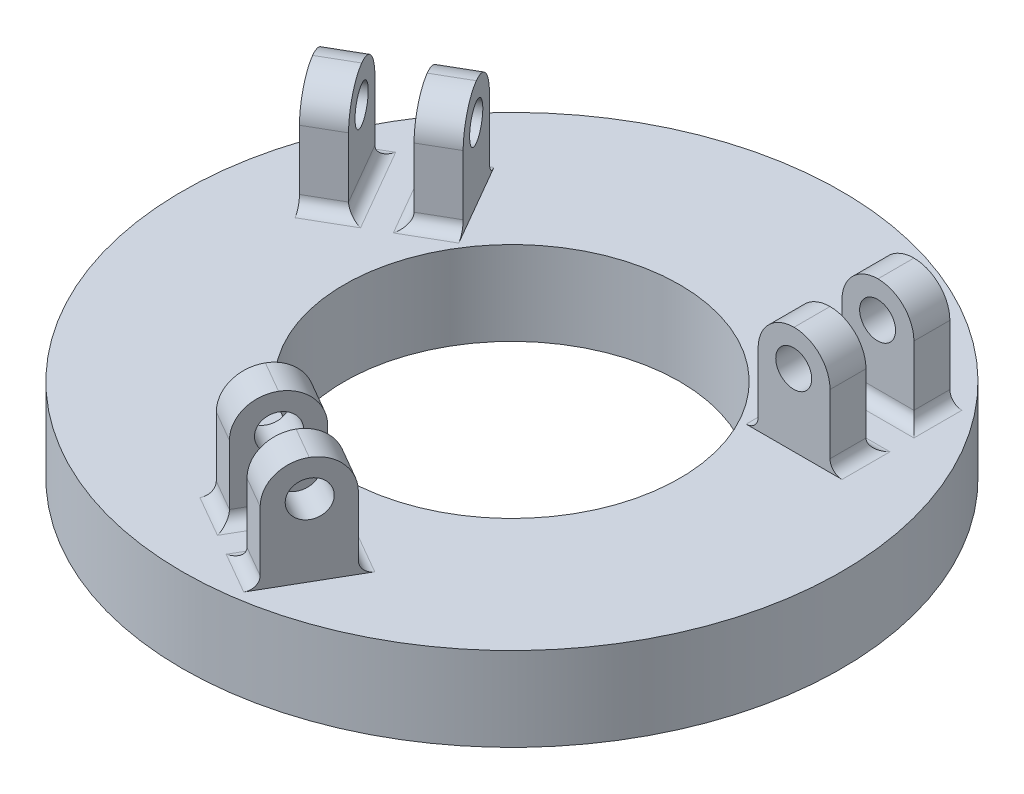
SolidWorks part; units mm, degrees
ref_plane "Front Plane" through (0, 0, 0) normal (0, 0, 1) x (1, 0, 0)
ref_plane "Top Plane" through (0, 0, 0) normal (0, 1, 0) x (1, 0, 0)
ref_plane "Right Plane" through (0, 0, 0) normal (1, 0, 0) x (0, 0, -1)
sketch "Sketch1" plane through (0, 0, 0) normal (0, 1, 0) x (1, 0, 0)
  line L0 (0, 0) -> (0, 14) construction
  circle A1 centre (0, 0) radius 14
  circle A7 centre (0, 0) radius 27.5
  point P4 (0, 22.2656)
  point P32 (0, 0)
  dimension "D1" = 55
  dimension "D2" = 28
extrude "Boss-Extrude1" add sketch "Sketch1" along normal blind 7
sketch "Sketch3" plane through (0, 7, 0) normal (0, 1, 0) x (1, 0, 0)
  line L0 (0, 21.4129) -> (0, 10.5871) construction
  line L6 (13.8521, 9.6899) -> (19.8521, 9.6899)
  line L11 (13.8521, 9.6899) -> (13.8521, 6.6899)
  line L12 (13.8521, 6.6899) -> (19.8521, 6.6899)
  line L13 (19.8521, 9.6899) -> (19.8521, 6.6899)
  line L14 (13.8521, 9.6899) -> (19.8521, 6.6899) construction
  line L15 (13.8521, 6.6899) -> (19.8521, 9.6899) construction
  line L16 (13.8521, 13.6899) -> (19.8521, 13.6899)
  line L17 (13.8521, 13.6899) -> (13.8521, 16.6899)
  line L18 (13.8521, 16.6899) -> (19.8521, 16.6899)
  line L19 (19.8521, 13.6899) -> (19.8521, 16.6899)
  line L20 (13.8521, 13.6899) -> (19.8521, 16.6899) construction
  line L21 (13.8521, 16.6899) -> (19.8521, 13.6899) construction
  point P0 (16.8521, 8.1899)
  point P5 (16.8521, 15.1899)
  point P13 (0, 0)
  point P14 (0, 0)
  dimension "D1" = 3
  dimension "D2" = 6
  dimension "D3" = 3
  dimension "D4" = 6
  dimension "D5" = 4
extrude "Boss-Extrude2" add sketch "Sketch3" along normal blind 9
fillet "Fillet1" radius 3 4 edges at (19.8521, 16, -8.1899) (13.8521, 16, -8.1899) (13.8521, 16, -15.1899) (19.8521, 16, -15.1899)
fillet "Fillet2" radius 1 6 edges at (16.8521, 7, -9.6899) (16.8521, 7, -13.6899) (19.8521, 7, -8.1899) (13.8521, 7, -8.1899) (13.8521, 7, -15.1899) (19.8521, 7, -15.1899)
sketch "Sketch5" plane through (0, 0, -6.6899) normal (0, 0, 1) x (1, 0, 0)
  circle A0 centre (16.8231, 13) radius 1.5
  dimension "D1" = 3
  dimension "D2" = 3
extrude "Cut-Extrude2" cut sketch "Sketch5" against normal through all both and the other way through all
pattern_circular "CirPattern2" count 3 over 360 about axis through (0, 7, 0) along (0, -1, 0) of "Boss-Extrude2", "Fillet1", "Fillet2", "Cut-Extrude2"
